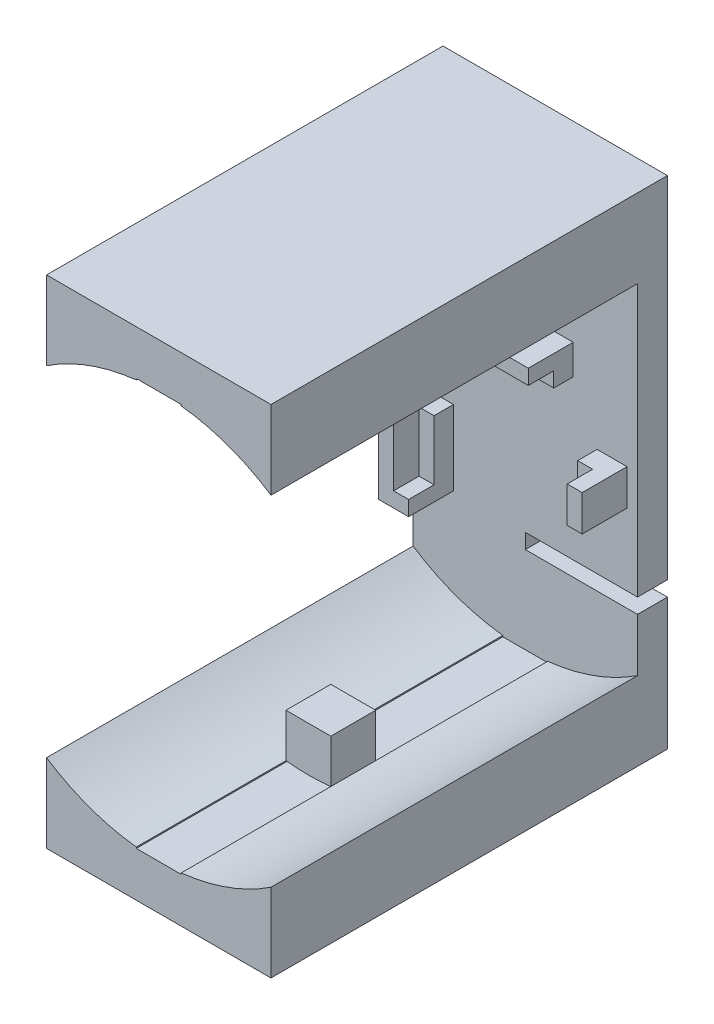
SolidWorks part; units mm, degrees
ref_plane "Front Plane" through (0, 0, 0) normal (0, 0, 1) x (1, 0, 0)
ref_plane "Top Plane" through (0, 0, 0) normal (0, 1, 0) x (1, 0, 0)
ref_plane "Right Plane" through (0, 0, 0) normal (1, 0, 0) x (0, 0, -1)
sketch "Sketch1" plane through (0, 0, 0) normal (0, 0, 1) x (1, 0, 0)
  line L0 (-5.7863, 0) -> (7.2515, 0) construction
  line L1 (-7.5, 16.6) -> (7.5, 16.6)
  line L2 (-7.5, 16.6) -> (-7.5, -16.6)
  line L3 (-7.5, -16.6) -> (7.5, -16.6)
  line L4 (7.5, 16.6) -> (7.5, -16.6)
  line L5 (0, 21.636) -> (0, -26241.9537) construction
  line L7 (-1.5, 13.6) -> (1.5, 13.6)
  line L8 (-1.5, 13.6) -> (-1.5, 10.6)
  line L9 (-1.5, 10.6) -> (1.5, 10.6)
  line L10 (1.5, 13.6) -> (1.5, 10.6)
  line L11 (-1.5, -10.6) -> (1.5, -10.6)
  line L12 (-1.5, -10.6) -> (-1.5, -13.6)
  line L13 (-1.5, -13.6) -> (1.5, -13.6)
  line L14 (1.5, -10.6) -> (1.5, -13.6)
  circle A0 centre (0, 0) radius 13.6
  point P11 (0, 16.6)
  point P12 (0, -16.6)
  point P21 (0, 13.6)
  point P22 (0, -13.6)
  point P23 (-7.5, 0)
  dimension "D1" = 27.2
  dimension "D2" = 3
  dimension "D3" = 3
  dimension "D4" = 15
extrude "Boss-Extrude1" add sketch "Sketch1" along normal blind 14.5 contours A0 L4 L1 L2 L8 L7 L10 | L10 A0 L8 L9 | L12 A0 L14 L11 | A0 L2 L3 L4 L14 L13 L12 region at (0, 14.6802, 0) region at (0, -14.6802, 0) region at (0, 12.0863, 0) region at (0, -12.0863, 0)
extrude "Boss-Extrude3" add sketch "Sketch1<3>" against normal blind 2 contours L4 A0 L10 L9 L8 L2 L12 L11 L14 | A0 L4 L1 L2 L8 L7 L10 | A0 L2 L3 L4 L14 L13 L12 | L8 L7 L10 L9 | L12 L11 L14 L13 region at (0, 14.6802, 0) region at (0, 0, 0) region at (0, -14.6802, 0)
sketch "Sketch1<3>" plane through (0, 0, 0) normal (0, 0, 1) x (1, 0, 0) same geometry as "Sketch1"
extrude "Cut-Extrude1" cut sketch "Sketch1<4>" along normal offset from surface (11.5 mm away) 3 contours L12 A0 L14 L11 | L10 A0 L8 L9 region at (0, 12.0863, 0) region at (0, -12.0863, 0) up to face at (0, -12.0793, 14.5)
sketch "Sketch1<4>" plane through (0, 0, 0) normal (0, 0, 1) x (1, 0, 0) same geometry as "Sketch1"
extrude "Boss-Extrude4" add sketch "Sketch1<5>" along normal offset from surface (24.5 mm away) 10 contours A0 L4 L1 L2 L8 L7 L10 | A0 L2 L3 L4 L14 L13 L12 region at (0, 14.6802, 0) region at (0, -14.6802, 0) up to face at (0, 13.8547, 14.5) offset beyond the face yes
sketch "Sketch1<5>" plane through (0, 0, 0) normal (0, 0, 1) x (1, 0, 0) same geometry as "Sketch1"
sketch "Sketch2" plane through (0, 0, 0) normal (0, 0, 1) x (1, 0, 0)
  line L0 (0, 0) -> (50000, 0) construction
  line L1 (-3.2, 5.8) -> (3.2, 5.8)
  line L2 (-3.2, 5.8) -> (-3.2, 4.8)
  line L3 (-3.2, 4.8) -> (3.2, 4.8)
  line L4 (3.2, 5.8) -> (3.2, 4.8)
  line L5 (-6.8, -1.8) -> (-4.8, -1.8)
  line L6 (-6.8, -1.8) -> (-6.8, -6.8)
  line L7 (-6.8, -6.8) -> (-4.8, -6.8)
  line L8 (-4.8, -1.8) -> (-4.8, -6.8)
  line L9 (-4.8, -1.8) -> (-5.8, -1.8)
  line L10 (-4.8, -1.8) -> (-4.8, -5.8)
  line L11 (-4.8, -5.8) -> (-5.8, -5.8)
  line L12 (-5.8, -1.8) -> (-5.8, -5.8)
  line L13 (6.8, 0.4) -> (4.8, 0.4)
  line L14 (6.8, 0.4) -> (6.8, -2)
  line L15 (6.8, -2) -> (4.8, -2)
  line L16 (4.8, 0.4) -> (4.8, -2)
  line L17 (6.8, 0.4) -> (5.8, 0.4)
  line L18 (6.8, 0.4) -> (6.8, -2)
  line L19 (6.8, -2) -> (5.8, -2)
  line L20 (5.8, 0.4) -> (5.8, -2)
  line L21 (-3.2, 5.8) -> (3.2, 5.8)
  line L22 (-3.2, 5.8) -> (-3.2, 3.8)
  line L23 (-3.2, 3.8) -> (3.2, 3.8)
  line L24 (3.2, 5.8) -> (3.2, 3.8)
  line L25 (0, 0) -> (0, 50000) construction
  line L26 (7.5, 11.345) -> (7.5, -11.345) construction
  line L27 (7.5, -6.8) -> (0, -6.8)
  line L28 (7.5, -6.8) -> (7.5, -7.8)
  line L29 (7.5, -7.8) -> (0, -7.8)
  line L30 (0, -6.8) -> (0, -7.8)
  point P24 (0, 3.8)
  point P25 (-5.8, -1.8)
  dimension "D1" = 4.8
  dimension "D2" = 6.4
  dimension "D3" = 1
  dimension "D4" = 1
  dimension "D5" = 0.4
  dimension "D6" = 2
  dimension "D7" = 1
  dimension "D8" = 1
  dimension "D9" = 5.8
  dimension "D10" = 5.8
  dimension "D11" = 1
  dimension "D12" = 1
  dimension "D13" = 5.8
  dimension "D14" = 1
  dimension "D15" = 4
  dimension "D17" = 1
extrude "Boss-Extrude5" add sketch "Sketch2" along normal blind 1.3 contours L5 L12 L11 L8 | L24 L3 L22 L23 | L20 L13 L16 L15 region at (0, 4.3, 0) region at (-5.3, -3.8, 0) region at (5.3, -0.8, 0)
extrude "Boss-Extrude6" add sketch "Sketch2<3>" along normal blind 3 contours L4 L1 L2 L3 | L12 L5 L6 L7 L8 L11 | L13 L20 L15 L14 region at (0, 5.3, 0) region at (-6.1333, -4.6333, 0) region at (6.3, -0.8, 0)
sketch "Sketch2<3>" plane through (0, 0, 0) normal (0, 0, 1) x (1, 0, 0) same geometry as "Sketch2"
extrude "Cut-Extrude2" cut sketch "Sketch2<4>" against normal through all contours L27 L30 L29 L28 region at (3.75, -7.3, 0)
sketch "Sketch2<4>" plane through (0, 0, 0) normal (0, 0, 1) x (1, 0, 0) same geometry as "Sketch2"
